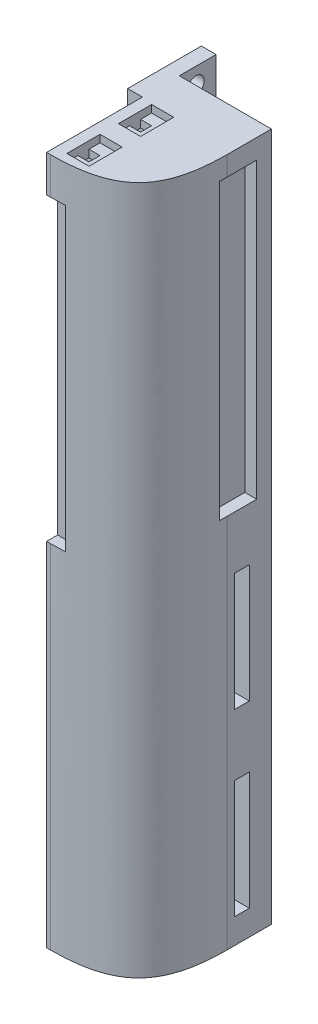
SolidWorks part; units mm, degrees
ref_plane "Front Plane" through (0, 0, 0) normal (0, 0, 1) x (1, 0, 0)
ref_plane "Top Plane" through (0, 0, 0) normal (0, 1, 0) x (1, 0, 0)
ref_plane "Right Plane" through (0, 0, 0) normal (1, 0, 0) x (0, 0, -1)
sketch "Sketch1" plane through (0, 0, 0) normal (0, 1, 0) x (1, 0, 0)
  line L1 (0, 0) -> (25, 0)
  line L2 (0, 0) -> (0, 36)
  line L3 (0, 36) -> (25, 36)
  line L4 (25, 0) -> (25, 36)
  dimension "D1" = 25
  dimension "D2" = 36
extrude "Boss-Extrude1" add sketch "Sketch1" along normal blind 186.9
fillet "Fillet1" radius 24 1 edges at (25, 93.45, 0) conic rho 0.55
ref_plane "Plane1" through (0, 0, 0) normal (0, 0, -1) x (-1, 0, 0)
sketch "Sketch2" plane through (0, 0, 0) normal (0, 0, -1) x (-1, 0, 0)
  line L1 (0, 176.9) -> (-5, 176.9)
  line L2 (0, 176.9) -> (0, 95.5)
  line L3 (0, 95.5) -> (-5, 95.5)
  line L4 (-5, 176.9) -> (-5, 95.5)
  line L5 (-1, 186.9) -> (-25, 186.9) construction
  dimension "D1" = 10
  dimension "D2" = 81.4
  dimension "D3" = 5
extrude "Cut-Extrude1" cut sketch "Sketch2" along normal blind 3
sketch "Sketch6" plane through (0, 0, -36) normal (0, 0, -1) x (-1, 0, 0)
  line L0 (0, 186.9) -> (0, 0) construction
  line L1 (0, 186.9) -> (4, 186.9)
  line L2 (0, 186.9) -> (0, 176.9)
  line L3 (0, 176.9) -> (4, 176.9)
  line L4 (4, 186.9) -> (4, 176.9)
  line L5 (0, 66.9) -> (4, 66.9)
  line L6 (0, 66.9) -> (0, 76.9)
  line L7 (0, 76.9) -> (4, 76.9)
  line L8 (4, 66.9) -> (4, 76.9)
  line L9 (-25, 186.9) -> (0, 186.9) construction
  dimension "D1" = 10
  dimension "D2" = 4
  dimension "D3" = 4
  dimension "D4" = 10
  dimension "D5" = 120
extrude "Boss-Extrude3" add sketch "Sketch6" against normal blind 10 and the other way blind 10
sketch "Sketch7" plane through (-4, 0, 0) normal (-1, 0, 0) x (0, 0, 1)
  line L0 (-36, 176.9) -> (-36, 76.9) construction
  line L1 (-46, 186.9) -> (-26, 186.9) construction
  line L2 (-46, 66.9) -> (-26, 66.9) construction
  line L3 (-36, 66.9) -> (-36, 0) construction
  circle A0 centre (-40.5, 182.4) radius 2.25
  circle A1 centre (-40.5, 71.4) radius 2.25
  dimension "D3" = 4.5
  dimension "D6" = 4.5
  dimension "D1" = 4.5
  dimension "D2" = 4.5
  dimension "D4" = 4.5
  dimension "D5" = 4.5
extrude "Cut-Extrude2" cut sketch "Sketch7" against normal up to next
chamfer "Chamfer1" distance 4 angle 45 1 edges at (0, 71.9, -26)
sketch "Sketch8" plane through (0, 0, 0) normal (-1, 0, 0) x (0, 0, 1)
  line L0 (-26, 186.9) -> (0, 186.9) construction
  line L1 (-10, 182.9) -> (-4, 182.9)
  line L2 (-10, 182.9) -> (-10, 178.9)
  line L3 (-10, 178.9) -> (-4, 178.9)
  line L4 (-4, 182.9) -> (-4, 178.9)
  line L5 (0, 13.75) -> (0, -13.75) construction
  line L7 (-24, 182.9) -> (-18, 182.9)
  line L8 (-24, 182.9) -> (-24, 178.9)
  line L9 (-24, 178.9) -> (-18, 178.9)
  line L10 (-18, 182.9) -> (-18, 178.9)
  dimension "D1" = 4
  dimension "D2" = 6
  dimension "D3" = 4
  dimension "D4" = 4
  dimension "D5" = 8
  dimension "D6" = 6
  dimension "D7" = 4
extrude "Cut-Extrude3" cut sketch "Sketch8" against normal blind 9
sketch "Sketch9" plane through (0, 186.9, 0) normal (0, 1, 0) x (1, 0, 0)
  line L0 (0, 0) -> (1, 0) construction
  line L1 (3, 5.5) -> (6, 5.5)
  line L2 (3, 5.5) -> (3, 8.5)
  line L3 (3, 8.5) -> (6, 8.5)
  line L4 (6, 5.5) -> (6, 8.5)
  line L5 (0, 26) -> (0, 0) construction
  line L7 (3, 19.5) -> (6, 19.5)
  line L8 (3, 19.5) -> (3, 22.5)
  line L9 (3, 22.5) -> (6, 22.5)
  line L10 (6, 19.5) -> (6, 22.5)
  dimension "D1" = 5.5
  dimension "D2" = 3
  dimension "D3" = 3
  dimension "D4" = 3
  dimension "D5" = 11
  dimension "D6" = 3
  dimension "D7" = 3
  dimension "D8" = 3
extrude "Cut-Extrude4" cut sketch "Sketch9" against normal blind 10
sketch "Sketch10" plane through (0, 0, 0) normal (0, -1, 0) x (1, 0, 0)
  line L0 (0, -36) -> (0, 0) construction
  line L1 (3, -5) -> (7, -5)
  line L2 (3, -5) -> (3, -33)
  line L3 (3, -33) -> (7, -33)
  line L4 (7, -5) -> (7, -29)
  line L5 (0, 0) -> (1, 0) construction
  line L6 (25, -36) -> (0, -36) construction
  line L7 (25, -24) -> (25, -36) construction
  line L8 (7, -33) -> (21, -33)
  line L10 (7, -29) -> (21, -29)
  line L11 (21, -33) -> (21, -29)
  dimension "D1" = 3
  dimension "D2" = 5
  dimension "D3" = 4
  dimension "D4" = 3
  dimension "D5" = 4
  dimension "D6" = 4
extrude "Boss-Extrude4" add sketch "Sketch10" along normal blind 4
sketch "Sketch11" plane through (0, 0, 0) normal (0, -1, 0) x (1, 0, 0)
  line L0 (21, -29) -> (7, -29) construction
  line L1 (7, -29) -> (7, -5) construction
  circle A0 centre (14, -22) radius 2
  dimension "D1" = 4
  dimension "D2" = 7
  dimension "D3" = 7
sketch "Sketch14" plane through (0, 0, 0) normal (0, 1, 0) x (-1, 0, 0)
  line L3 (0, -26) -> (0, 0) construction
  line L4 (-13.75, 0) -> (13.75, 0) construction
  circle A1 centre (-14, -11) radius 1.5
  dimension "D1" = 11
  dimension "D2" = 14
  dimension "D6" = 3
extrude "Cut-Extrude5" cut sketch "Sketch11" against normal blind 5
extrude "Cut-Extrude6" cut sketch "Sketch14" along normal blind 4
sketch "Sketch15" plane through (25, 0, 0) normal (1, 0, 0) x (0, 0, -1)
  line L0 (24, 186.9) -> (24, 0) construction
  line L1 (26, 87.5) -> (30, 87.5)
  line L2 (26, 87.5) -> (26, 55.5)
  line L3 (26, 55.5) -> (30, 55.5)
  line L4 (30, 87.5) -> (30, 55.5)
  line L6 (29, -4) -> (5, -4) construction
  line L7 (26, 38.8) -> (30, 38.8)
  line L8 (26, 38.8) -> (26, 6.8)
  line L9 (26, 6.8) -> (30, 6.8)
  line L10 (30, 38.8) -> (30, 6.8)
  dimension "D1" = 2
  dimension "D2" = 4
  dimension "D3" = 10.8
  dimension "D4" = 32
  dimension "D5" = 2
  dimension "D6" = 4
  dimension "D7" = 32
  dimension "D8" = 16.7
extrude "Cut-Extrude7" cut sketch "Sketch15" against normal blind 4
sketch "Sketch16" plane through (25, 0, 0) normal (1, 0, 0) x (0, 0, -1)
  line L0 (36, 186.9) -> (36, 0) construction
  line L1 (32, 181.6) -> (22, 181.6)
  line L2 (32, 181.6) -> (32, 101.9)
  line L3 (32, 101.9) -> (22, 101.9)
  line L4 (22, 181.6) -> (22, 101.9)
  line L5 (24, 186.9) -> (36, 186.9) construction
  dimension "D1" = 4
  dimension "D2" = 5.3
  dimension "D3" = 10
  dimension "D4" = 79.7
extrude "Cut-Extrude8" cut sketch "Sketch16" against normal blind 3.2
sketch "Sketch17" plane through (0, 186.9, 0) normal (0, 1, 0) x (1, 0, 0)
  line L0 (6, 8.5) -> (3, 8.5) construction
  line L1 (3, 25.5) -> (9, 25.5)
  line L2 (3, 25.5) -> (3, 16.5)
  line L3 (3, 16.5) -> (9, 16.5)
  line L4 (9, 25.5) -> (9, 16.5)
  line L5 (3, 11.5) -> (9, 11.5)
  line L6 (3, 11.5) -> (3, 2.5)
  line L7 (3, 2.5) -> (9, 2.5)
  line L8 (9, 11.5) -> (9, 2.5)
  line L9 (6, 5.5) -> (6, 8.5) construction
  line L10 (3, 5.5) -> (6, 5.5) construction
  line L11 (3, 8.5) -> (3, 5.5) construction
  line L12 (3, 22.5) -> (3, 19.5) construction
  line L13 (6, 22.5) -> (3, 22.5) construction
  line L14 (6, 19.5) -> (6, 22.5) construction
  line L15 (3, 19.5) -> (6, 19.5) construction
  dimension "D1" = 3
  dimension "D2" = 3
  dimension "D3" = 3
  dimension "D4" = 0
  dimension "D5" = 0
  dimension "D6" = 3
  dimension "D7" = 3
  dimension "D8" = 3
extrude "Cut-Extrude9" cut sketch "Sketch17" against normal blind 2
